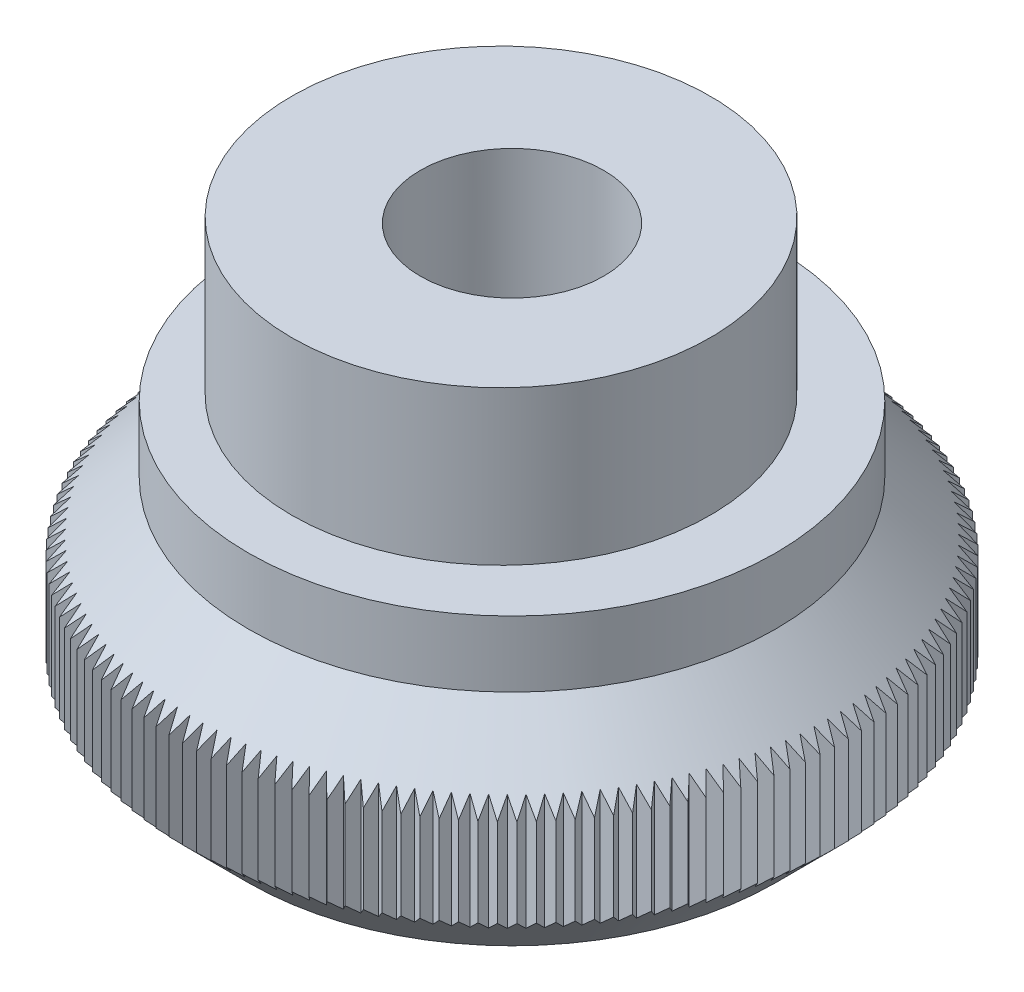
SolidWorks part; units mm, degrees
ref_plane "Front Plane" through (0, 0, 0) normal (0, 0, 1) x (1, 0, 0)
ref_plane "Top Plane" through (0, 0, 0) normal (0, 1, 0) x (1, 0, 0)
ref_plane "Right Plane" through (0, 0, 0) normal (1, 0, 0) x (0, 0, -1)
sketch "Sketch1" plane through (0, 0, 0) normal (0, 1, 0) x (1, 0, 0)
  circle A0 centre (0, 0) radius 15
  circle A1 centre (0, 0) radius 4.175
  dimension "D1" = 30
  dimension "D2" = 8.35
extrude "Boss-Extrude1" add sketch "Sketch1" along normal blind 10
sketch "Sketch2" plane through (0, 10, 0) normal (0, 1, 0) x (1, 0, 0)
  line L0 (0, 0) -> (-0.5, 0)
  circle A0 centre (-0.5, 0) radius 9.525
  circle M2 centre (0, 0) radius 4.175
  dimension "D1" = 19.05
extrude "Boss-Extrude2" add sketch "Sketch2" along normal blind 10 contours A0 M2 region at (-9.7556, 10, 0)
chamfer "Chamfer1" distance 3 angle 45 2 edges at (0, 10, 15) (0, 0, 15)
sketch "Sketch4" plane through (0, 0, 0) normal (0, -1, 0) x (1, 0, 0)
  circle A0 centre (0, 0) radius 5.5
  dimension "D1" = 11
extrude "Cut-Extrude1" cut sketch "Sketch4" against normal blind 12.5
sketch "Sketch5" plane through (0, 10, 0) normal (0, 1, 0) x (1, 0, 0)
  line L0 (0, 0) -> (0, 15) construction
  line L1 (0, 15) -> (-0.3122, 14.3338)
  line L2 (0, 15) -> (0.3122, 14.3338)
  line L3 (0.6281, 14.9868) -> (0.2883, 14.3343)
  line L4 (0.6281, 14.9868) -> (0.9122, 14.3082)
  line L5 (1.2552, 14.9474) -> (0.8883, 14.3097)
  line L6 (1.2552, 14.9474) -> (1.5105, 14.2574)
  line L7 (1.88, 14.8817) -> (1.4868, 14.2599)
  line L8 (1.88, 14.8817) -> (2.1062, 14.1816)
  line L9 (2.5015, 14.7899) -> (2.0826, 14.1851)
  line L10 (2.5015, 14.7899) -> (2.6983, 14.081)
  line L11 (3.1187, 14.6722) -> (2.6748, 14.0855)
  line L12 (3.1187, 14.6722) -> (3.2855, 13.9557)
  line L13 (3.7303, 14.5287) -> (3.2623, 13.9611)
  line L14 (3.7303, 14.5287) -> (3.8671, 13.8058)
  line L15 (4.3355, 14.3598) -> (3.844, 13.8123)
  line L16 (4.3355, 14.3598) -> (4.4418, 13.6318)
  line L17 (4.933, 14.1656) -> (4.4191, 13.6392)
  line L18 (4.933, 14.1656) -> (5.0088, 13.4338)
  line L19 (5.5219, 13.9466) -> (4.9863, 13.4422)
  line L20 (5.5219, 13.9466) -> (5.5669, 13.2123)
  line L21 (6.101, 13.7032) -> (5.5449, 13.2216)
  line L22 (6.101, 13.7032) -> (6.1153, 12.9676)
  line L23 (6.6695, 13.4357) -> (6.0937, 12.9778)
  line L24 (6.6695, 13.4357) -> (6.653, 12.7001)
  line L25 (7.2263, 13.1446) -> (6.6318, 12.7112)
  line L26 (7.2263, 13.1446) -> (7.179, 12.4104)
  line L27 (7.7704, 12.8305) -> (7.1582, 12.4224)
  line L28 (7.7704, 12.8305) -> (7.6923, 12.0989)
  line L29 (8.3009, 12.4938) -> (7.6722, 12.1117)
  line L30 (8.3009, 12.4938) -> (8.1922, 11.7662)
  line L31 (8.8168, 12.1353) -> (8.1726, 11.7798)
  line L32 (8.8168, 12.1353) -> (8.6778, 11.4128)
  line L33 (9.3172, 11.7554) -> (8.6587, 11.4272)
  line L34 (9.3172, 11.7554) -> (9.1481, 11.0394)
  line L35 (9.8013, 11.3549) -> (9.1297, 11.0546)
  line L36 (9.8013, 11.3549) -> (9.6023, 10.6466)
  line L37 (10.2682, 10.9345) -> (9.5846, 10.6626)
  line L38 (10.2682, 10.9345) -> (10.0398, 10.2352)
  line L39 (10.7171, 10.495) -> (10.0227, 10.2519)
  line L40 (10.7171, 10.495) -> (10.4595, 9.8058)
  line L41 (11.1472, 10.037) -> (10.4432, 9.8232)
  line L42 (11.1472, 10.037) -> (10.861, 9.3592)
  line L43 (11.5577, 9.5614) -> (10.8454, 9.3773)
  line L44 (11.5577, 9.5614) -> (11.2434, 8.8961)
  line L45 (11.9479, 9.069) -> (11.2285, 8.9149)
  line L46 (11.9479, 9.069) -> (11.6061, 8.4175)
  line L47 (12.3172, 8.5607) -> (11.592, 8.4369)
  line L48 (12.3172, 8.5607) -> (11.9484, 7.9241)
  line L49 (12.6649, 8.0374) -> (11.9351, 7.944)
  line L50 (12.6649, 8.0374) -> (12.2697, 7.4168)
  line L51 (12.9904, 7.5) -> (12.2573, 7.4373)
  line L52 (12.9904, 7.5) -> (12.5695, 6.8965)
  line L53 (13.2931, 6.9494) -> (12.558, 6.9175)
  line L54 (13.2931, 6.9494) -> (12.8473, 6.3641)
  line L55 (13.5724, 6.3867) -> (12.8367, 6.3855)
  line L56 (13.5724, 6.3867) -> (13.1025, 5.8205)
  line L57 (13.8279, 5.8127) -> (13.0928, 5.8424)
  line L58 (13.8279, 5.8127) -> (13.3348, 5.2668)
  line L59 (14.0592, 5.2286) -> (13.326, 5.289)
  line L60 (14.0592, 5.2286) -> (13.5436, 4.7037)
  line L61 (14.2658, 4.6353) -> (13.5358, 4.7263)
  line L62 (14.2658, 4.6353) -> (13.7287, 4.1325)
  line L63 (14.4474, 4.0338) -> (13.7218, 4.1553)
  line L64 (14.4474, 4.0338) -> (13.8897, 3.5539)
  line L65 (14.6037, 3.4253) -> (13.8838, 3.5771)
  line L66 (14.6037, 3.4253) -> (14.0264, 2.9692)
  line L67 (14.7343, 2.8107) -> (14.0214, 2.9926)
  line L68 (14.7343, 2.8107) -> (14.1384, 2.3792)
  line L69 (14.8391, 2.1912) -> (14.1344, 2.4028)
  line L70 (14.8391, 2.1912) -> (14.2256, 1.7851)
  line L71 (14.9178, 1.5679) -> (14.2226, 1.8088)
  line L72 (14.9178, 1.5679) -> (14.2879, 1.1878)
  line L73 (14.9704, 0.9419) -> (14.2859, 1.2116)
  line L74 (14.9704, 0.9419) -> (14.3251, 0.5884)
  line L75 (14.9967, 0.3141) -> (14.3241, 0.6123)
  line L76 (14.9967, 0.3141) -> (14.3372, -0.012)
  line L77 (14.9967, -0.3141) -> (14.3372, 0.012)
  line L78 (14.9967, -0.3141) -> (14.3241, -0.6123)
  line L79 (14.9704, -0.9419) -> (14.3251, -0.5884)
  line L80 (14.9704, -0.9419) -> (14.2859, -1.2116)
  line L81 (14.9178, -1.5679) -> (14.2879, -1.1878)
  line L82 (14.9178, -1.5679) -> (14.2226, -1.8088)
  line L83 (14.8391, -2.1912) -> (14.2256, -1.7851)
  line L84 (14.8391, -2.1912) -> (14.1344, -2.4028)
  line L85 (14.7343, -2.8107) -> (14.1384, -2.3792)
  line L86 (14.7343, -2.8107) -> (14.0214, -2.9926)
  line L87 (14.6037, -3.4253) -> (14.0264, -2.9692)
  line L88 (14.6037, -3.4253) -> (13.8838, -3.5771)
  line L89 (14.4474, -4.0338) -> (13.8897, -3.5539)
  line L90 (14.4474, -4.0338) -> (13.7218, -4.1553)
  line L91 (14.2658, -4.6353) -> (13.7287, -4.1325)
  line L92 (14.2658, -4.6353) -> (13.5358, -4.7263)
  line L93 (14.0592, -5.2286) -> (13.5436, -4.7037)
  line L94 (14.0592, -5.2286) -> (13.326, -5.289)
  line L95 (13.8279, -5.8127) -> (13.3348, -5.2668)
  line L96 (13.8279, -5.8127) -> (13.0928, -5.8424)
  line L97 (13.5724, -6.3867) -> (13.1025, -5.8205)
  line L98 (13.5724, -6.3867) -> (12.8367, -6.3855)
  line L99 (13.2931, -6.9494) -> (12.8473, -6.3641)
  line L100 (13.2931, -6.9494) -> (12.558, -6.9175)
  line L101 (12.9904, -7.5) -> (12.5695, -6.8965)
  line L102 (12.9904, -7.5) -> (12.2573, -7.4373)
  line L103 (12.6649, -8.0374) -> (12.2697, -7.4168)
  line L104 (12.6649, -8.0374) -> (11.9351, -7.944)
  line L105 (12.3172, -8.5607) -> (11.9484, -7.9241)
  line L106 (12.3172, -8.5607) -> (11.592, -8.4369)
  line L107 (11.9479, -9.069) -> (11.6061, -8.4175)
  line L108 (11.9479, -9.069) -> (11.2285, -8.9149)
  line L109 (11.5577, -9.5614) -> (11.2434, -8.8961)
  line L110 (11.5577, -9.5614) -> (10.8454, -9.3773)
  line L111 (11.1472, -10.037) -> (10.861, -9.3592)
  line L112 (11.1472, -10.037) -> (10.4432, -9.8232)
  line L113 (10.7171, -10.495) -> (10.4595, -9.8058)
  line L114 (10.7171, -10.495) -> (10.0227, -10.2519)
  line L115 (10.2682, -10.9345) -> (10.0398, -10.2352)
  line L116 (10.2682, -10.9345) -> (9.5846, -10.6626)
  line L117 (9.8013, -11.3549) -> (9.6023, -10.6466)
  line L118 (9.8013, -11.3549) -> (9.1297, -11.0546)
  line L119 (9.3172, -11.7554) -> (9.1481, -11.0394)
  line L120 (9.3172, -11.7554) -> (8.6587, -11.4272)
  line L121 (8.8168, -12.1353) -> (8.6778, -11.4128)
  line L122 (8.8168, -12.1353) -> (8.1726, -11.7798)
  line L123 (8.3009, -12.4938) -> (8.1922, -11.7662)
  line L124 (8.3009, -12.4938) -> (7.6722, -12.1117)
  line L125 (7.7704, -12.8305) -> (7.6923, -12.0989)
  line L126 (7.7704, -12.8305) -> (7.1582, -12.4224)
  line L127 (7.2263, -13.1446) -> (7.179, -12.4104)
  line L128 (7.2263, -13.1446) -> (6.6318, -12.7112)
  line L129 (6.6695, -13.4357) -> (6.653, -12.7001)
  line L130 (6.6695, -13.4357) -> (6.0937, -12.9778)
  line L131 (6.101, -13.7032) -> (6.1153, -12.9676)
  line L132 (6.101, -13.7032) -> (5.5449, -13.2216)
  line L133 (5.5219, -13.9466) -> (5.5669, -13.2123)
  line L134 (5.5219, -13.9466) -> (4.9863, -13.4422)
  line L135 (4.933, -14.1656) -> (5.0088, -13.4338)
  line L136 (4.933, -14.1656) -> (4.4191, -13.6392)
  line L137 (4.3355, -14.3598) -> (4.4418, -13.6318)
  line L138 (4.3355, -14.3598) -> (3.844, -13.8123)
  line L139 (3.7303, -14.5287) -> (3.8671, -13.8058)
  line L140 (3.7303, -14.5287) -> (3.2623, -13.9611)
  line L141 (3.1187, -14.6722) -> (3.2855, -13.9557)
  line L142 (3.1187, -14.6722) -> (2.6748, -14.0855)
  line L143 (2.5015, -14.7899) -> (2.6983, -14.081)
  line L144 (2.5015, -14.7899) -> (2.0826, -14.1851)
  line L145 (1.88, -14.8817) -> (2.1062, -14.1816)
  line L146 (1.88, -14.8817) -> (1.4868, -14.2599)
  line L147 (1.2552, -14.9474) -> (1.5105, -14.2574)
  line L148 (1.2552, -14.9474) -> (0.8883, -14.3097)
  line L149 (0.6281, -14.9868) -> (0.9122, -14.3082)
  line L150 (0.6281, -14.9868) -> (0.2883, -14.3343)
  line L151 (0, -15) -> (0.3122, -14.3338)
  line L152 (0, -15) -> (-0.3122, -14.3338)
  line L153 (-0.6281, -14.9868) -> (-0.2883, -14.3343)
  line L154 (-0.6281, -14.9868) -> (-0.9122, -14.3082)
  line L155 (-1.2552, -14.9474) -> (-0.8883, -14.3097)
  line L156 (-1.2552, -14.9474) -> (-1.5105, -14.2574)
  line L157 (-1.88, -14.8817) -> (-1.4868, -14.2599)
  line L158 (-1.88, -14.8817) -> (-2.1062, -14.1816)
  line L159 (-2.5015, -14.7899) -> (-2.0826, -14.1851)
  line L160 (-2.5015, -14.7899) -> (-2.6983, -14.081)
  line L161 (-3.1187, -14.6722) -> (-2.6748, -14.0855)
  line L162 (-3.1187, -14.6722) -> (-3.2855, -13.9557)
  line L163 (-3.7303, -14.5287) -> (-3.2623, -13.9611)
  line L164 (-3.7303, -14.5287) -> (-3.8671, -13.8058)
  line L165 (-4.3355, -14.3598) -> (-3.844, -13.8123)
  line L166 (-4.3355, -14.3598) -> (-4.4418, -13.6318)
  line L167 (-4.933, -14.1656) -> (-4.4191, -13.6392)
  line L168 (-4.933, -14.1656) -> (-5.0088, -13.4338)
  line L169 (-5.5219, -13.9466) -> (-4.9863, -13.4422)
  line L170 (-5.5219, -13.9466) -> (-5.5669, -13.2123)
  line L171 (-6.101, -13.7032) -> (-5.5449, -13.2216)
  line L172 (-6.101, -13.7032) -> (-6.1153, -12.9676)
  line L173 (-6.6695, -13.4357) -> (-6.0937, -12.9778)
  line L174 (-6.6695, -13.4357) -> (-6.653, -12.7001)
  line L175 (-7.2263, -13.1446) -> (-6.6318, -12.7112)
  line L176 (-7.2263, -13.1446) -> (-7.179, -12.4104)
  line L177 (-7.7704, -12.8305) -> (-7.1582, -12.4224)
  line L178 (-7.7704, -12.8305) -> (-7.6923, -12.0989)
  line L179 (-8.3009, -12.4938) -> (-7.6722, -12.1117)
  line L180 (-8.3009, -12.4938) -> (-8.1922, -11.7662)
  line L181 (-8.8168, -12.1353) -> (-8.1726, -11.7798)
  line L182 (-8.8168, -12.1353) -> (-8.6778, -11.4128)
  line L183 (-9.3172, -11.7554) -> (-8.6587, -11.4272)
  line L184 (-9.3172, -11.7554) -> (-9.1481, -11.0394)
  line L185 (-9.8013, -11.3549) -> (-9.1297, -11.0546)
  line L186 (-9.8013, -11.3549) -> (-9.6023, -10.6466)
  line L187 (-10.2682, -10.9345) -> (-9.5846, -10.6626)
  line L188 (-10.2682, -10.9345) -> (-10.0398, -10.2352)
  line L189 (-10.7171, -10.495) -> (-10.0227, -10.2519)
  line L190 (-10.7171, -10.495) -> (-10.4595, -9.8058)
  line L191 (-11.1472, -10.037) -> (-10.4432, -9.8232)
  line L192 (-11.1472, -10.037) -> (-10.861, -9.3592)
  line L193 (-11.5577, -9.5614) -> (-10.8454, -9.3773)
  line L194 (-11.5577, -9.5614) -> (-11.2434, -8.8961)
  line L195 (-11.9479, -9.069) -> (-11.2285, -8.9149)
  line L196 (-11.9479, -9.069) -> (-11.6061, -8.4175)
  line L197 (-12.3172, -8.5607) -> (-11.592, -8.4369)
  line L198 (-12.3172, -8.5607) -> (-11.9484, -7.9241)
  line L199 (-12.6649, -8.0374) -> (-11.9351, -7.944)
  line L200 (-12.6649, -8.0374) -> (-12.2697, -7.4168)
  line L201 (-12.9904, -7.5) -> (-12.2573, -7.4373)
  line L202 (-12.9904, -7.5) -> (-12.5695, -6.8965)
  line L203 (-13.2931, -6.9494) -> (-12.558, -6.9175)
  line L204 (-13.2931, -6.9494) -> (-12.8473, -6.3641)
  line L205 (-13.5724, -6.3867) -> (-12.8367, -6.3855)
  line L206 (-13.5724, -6.3867) -> (-13.1025, -5.8205)
  line L207 (-13.8279, -5.8127) -> (-13.0928, -5.8424)
  line L208 (-13.8279, -5.8127) -> (-13.3348, -5.2668)
  line L209 (-14.0592, -5.2286) -> (-13.326, -5.289)
  line L210 (-14.0592, -5.2286) -> (-13.5436, -4.7037)
  line L211 (-14.2658, -4.6353) -> (-13.5358, -4.7263)
  line L212 (-14.2658, -4.6353) -> (-13.7287, -4.1325)
  line L213 (-14.4474, -4.0338) -> (-13.7218, -4.1553)
  line L214 (-14.4474, -4.0338) -> (-13.8897, -3.5539)
  line L215 (-14.6037, -3.4253) -> (-13.8838, -3.5771)
  line L216 (-14.6037, -3.4253) -> (-14.0264, -2.9692)
  line L217 (-14.7343, -2.8107) -> (-14.0214, -2.9926)
  line L218 (-14.7343, -2.8107) -> (-14.1384, -2.3792)
  line L219 (-14.8391, -2.1912) -> (-14.1344, -2.4028)
  line L220 (-14.8391, -2.1912) -> (-14.2256, -1.7851)
  line L221 (-14.9178, -1.5679) -> (-14.2226, -1.8088)
  line L222 (-14.9178, -1.5679) -> (-14.2879, -1.1878)
  line L223 (-14.9704, -0.9419) -> (-14.2859, -1.2116)
  line L224 (-14.9704, -0.9419) -> (-14.3251, -0.5884)
  line L225 (-14.9967, -0.3141) -> (-14.3241, -0.6123)
  line L226 (-14.9967, -0.3141) -> (-14.3372, 0.012)
  line L227 (-14.9967, 0.3141) -> (-14.3372, -0.012)
  line L228 (-14.9967, 0.3141) -> (-14.3241, 0.6123)
  line L229 (-14.9704, 0.9419) -> (-14.3251, 0.5884)
  line L230 (-14.9704, 0.9419) -> (-14.2859, 1.2116)
  line L231 (-14.9178, 1.5679) -> (-14.2879, 1.1878)
  line L232 (-14.9178, 1.5679) -> (-14.2226, 1.8088)
  line L233 (-14.8391, 2.1912) -> (-14.2256, 1.7851)
  line L234 (-14.8391, 2.1912) -> (-14.1344, 2.4028)
  line L235 (-14.7343, 2.8107) -> (-14.1384, 2.3792)
  line L236 (-14.7343, 2.8107) -> (-14.0214, 2.9926)
  line L237 (-14.6037, 3.4253) -> (-14.0264, 2.9692)
  line L238 (-14.6037, 3.4253) -> (-13.8838, 3.5771)
  line L239 (-14.4474, 4.0338) -> (-13.8897, 3.5539)
  line L240 (-14.4474, 4.0338) -> (-13.7218, 4.1553)
  line L241 (-14.2658, 4.6353) -> (-13.7287, 4.1325)
  line L242 (-14.2658, 4.6353) -> (-13.5358, 4.7263)
  line L243 (-14.0592, 5.2286) -> (-13.5436, 4.7037)
  line L244 (-14.0592, 5.2286) -> (-13.326, 5.289)
  line L245 (-13.8279, 5.8127) -> (-13.3348, 5.2668)
  line L246 (-13.8279, 5.8127) -> (-13.0928, 5.8424)
  line L247 (-13.5724, 6.3867) -> (-13.1025, 5.8205)
  line L248 (-13.5724, 6.3867) -> (-12.8367, 6.3855)
  line L249 (-13.2931, 6.9494) -> (-12.8473, 6.3641)
  line L250 (-13.2931, 6.9494) -> (-12.558, 6.9175)
  line L251 (-12.9904, 7.5) -> (-12.5695, 6.8965)
  line L252 (-12.9904, 7.5) -> (-12.2573, 7.4373)
  line L253 (-12.6649, 8.0374) -> (-12.2697, 7.4168)
  line L254 (-12.6649, 8.0374) -> (-11.9351, 7.944)
  line L255 (-12.3172, 8.5607) -> (-11.9484, 7.9241)
  line L256 (-12.3172, 8.5607) -> (-11.592, 8.4369)
  line L257 (-11.9479, 9.069) -> (-11.6061, 8.4175)
  line L258 (-11.9479, 9.069) -> (-11.2285, 8.9149)
  line L259 (-11.5577, 9.5614) -> (-11.2434, 8.8961)
  line L260 (-11.5577, 9.5614) -> (-10.8454, 9.3773)
  line L261 (-11.1472, 10.037) -> (-10.861, 9.3592)
  line L262 (-11.1472, 10.037) -> (-10.4432, 9.8232)
  line L263 (-10.7171, 10.495) -> (-10.4595, 9.8058)
  line L264 (-10.7171, 10.495) -> (-10.0227, 10.2519)
  line L265 (-10.2682, 10.9345) -> (-10.0398, 10.2352)
  line L266 (-10.2682, 10.9345) -> (-9.5846, 10.6626)
  line L267 (-9.8013, 11.3549) -> (-9.6023, 10.6466)
  line L268 (-9.8013, 11.3549) -> (-9.1297, 11.0546)
  line L269 (-9.3172, 11.7554) -> (-9.1481, 11.0394)
  line L270 (-9.3172, 11.7554) -> (-8.6587, 11.4272)
  line L271 (-8.8168, 12.1353) -> (-8.6778, 11.4128)
  line L272 (-8.8168, 12.1353) -> (-8.1726, 11.7798)
  line L273 (-8.3009, 12.4938) -> (-8.1922, 11.7662)
  line L274 (-8.3009, 12.4938) -> (-7.6722, 12.1117)
  line L275 (-7.7704, 12.8305) -> (-7.6923, 12.0989)
  line L276 (-7.7704, 12.8305) -> (-7.1582, 12.4224)
  line L277 (-7.2263, 13.1446) -> (-7.179, 12.4104)
  line L278 (-7.2263, 13.1446) -> (-6.6318, 12.7112)
  line L279 (-6.6695, 13.4357) -> (-6.653, 12.7001)
  line L280 (-6.6695, 13.4357) -> (-6.0937, 12.9778)
  line L281 (-6.101, 13.7032) -> (-6.1153, 12.9676)
  line L282 (-6.101, 13.7032) -> (-5.5449, 13.2216)
  line L283 (-5.5219, 13.9466) -> (-5.5669, 13.2123)
  line L284 (-5.5219, 13.9466) -> (-4.9863, 13.4422)
  line L285 (-4.933, 14.1656) -> (-5.0088, 13.4338)
  line L286 (-4.933, 14.1656) -> (-4.4191, 13.6392)
  line L287 (-4.3355, 14.3598) -> (-4.4418, 13.6318)
  line L288 (-4.3355, 14.3598) -> (-3.844, 13.8123)
  line L289 (-3.7303, 14.5287) -> (-3.8671, 13.8058)
  line L290 (-3.7303, 14.5287) -> (-3.2623, 13.9611)
  line L291 (-3.1187, 14.6722) -> (-3.2855, 13.9557)
  line L292 (-3.1187, 14.6722) -> (-2.6748, 14.0855)
  line L293 (-2.5015, 14.7899) -> (-2.6983, 14.081)
  line L294 (-2.5015, 14.7899) -> (-2.0826, 14.1851)
  line L295 (-1.88, 14.8817) -> (-2.1062, 14.1816)
  line L296 (-1.88, 14.8817) -> (-1.4868, 14.2599)
  line L297 (-1.2552, 14.9474) -> (-1.5105, 14.2574)
  line L298 (-1.2552, 14.9474) -> (-0.8883, 14.3097)
  line L299 (-0.6281, 14.9868) -> (-0.9122, 14.3082)
  line L300 (-0.6281, 14.9868) -> (-0.2883, 14.3343)
  circle A0 centre (0, 0) radius 15 construction
  circle A1 centre (0, 0) radius 18.3592
  dimension "D1" = 150
extrude "Cut-Extrude2" cut sketch "Sketch5" against normal through all contours A1 L299 L300 L1 L2 L3 L4 L5 L6 L7 L8 L9 L10 L11 L12 L13 L14 L15 L16 L17 L18 L19 L20 L21 L22 L23 L24 L25 L26 L27 L28 L29 L30 L31 L32 L33 L34 L35 L36 L37 L38 L39 L40 L41 L42 L43 L44 L45 L46 L47 region at (-17.8399, 10, 0)
sketch "Sketch6" plane through (0, 10, 0) normal (0, 1, 0) x (1, 0, 0)
  circle A0 centre (0, 0) radius 12
  circle A1 centre (-0.5, 0) radius 9.525
extrude "Boss-Extrude3" add sketch "Sketch6" along normal blind 3
sketch "Sketch7" plane through (0, 12.5, 0) normal (0, -1, 0) x (1, 0, 0)
  circle A0 centre (0, 0) radius 4.175
extrude "Boss-Extrude4" add sketch "Sketch7" against normal blind 1
